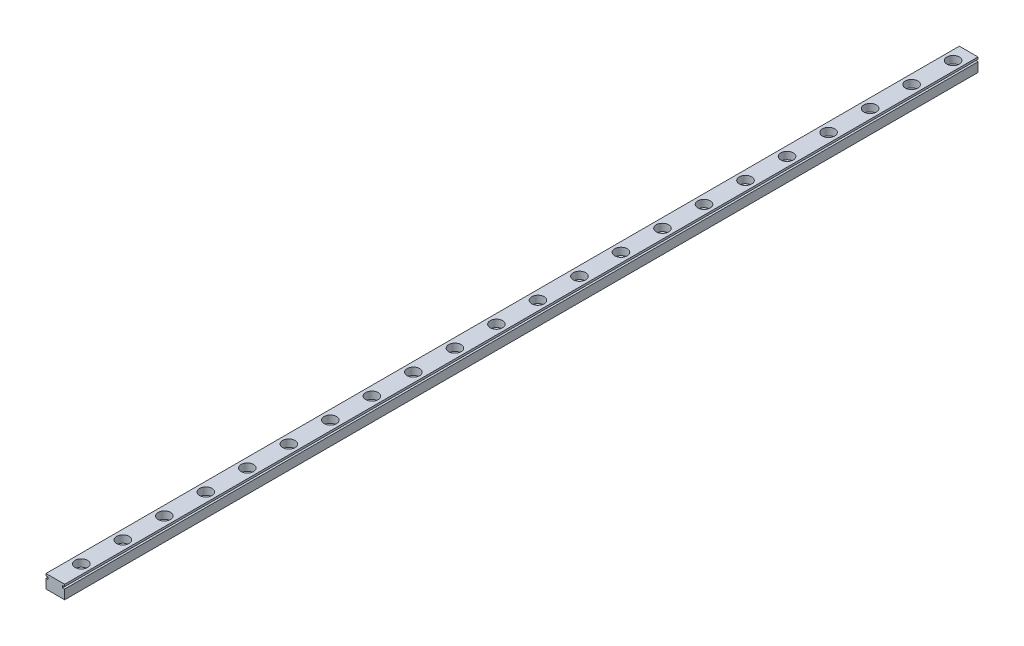
SolidWorks part; units mm, degrees
material "1.0401 (C15)"
ref_plane "前视基准面" through (0, 0, 0) normal (0, 0, 1) x (1, 0, 0)
ref_plane "上视基准面" through (0, 0, 0) normal (0, 1, 0) x (1, 0, 0)
ref_plane "右视基准面" through (0, 0, 0) normal (1, 0, 0) x (0, 0, -1)
sketch "草图1" plane through (0, 0, 0) normal (0, 0, 1) x (1, 0, 0)
  line L0 (0, -0.8589) -> (0, 7.8911) construction
  line L1 (-4.5, 0) -> (4.5, 0)
  line L2 (4.5, 0) -> (4.5, 4.5)
  line L3 (4.5, 5.5) -> (3.5, 5.5)
  line L4 (3.5, 5.5) -> (3.5, 4.5)
  line L5 (4.5, 5.5) -> (4.5, 6.5)
  line L6 (4.5, 6.5) -> (-4.5, 6.5)
  line L7 (3.5, 4.5) -> (4.5, 4.5)
  line L8 (-4.5, 0) -> (-4.5, 4.5)
  line L9 (-3.5, 4.5) -> (-4.5, 4.5)
  line L10 (-3.5, 5.5) -> (-3.5, 4.5)
  line L11 (-4.5, 5.5) -> (-3.5, 5.5)
  line L12 (-4.5, 5.5) -> (-4.5, 6.5)
  point P12 (0, 0)
  point P17 (0, 6.5)
  dimension "D1" = 4.5
  dimension "D2" = 6.5
  dimension "D3" = 1
  dimension "D4" = 1
  dimension "D5" = 1
  dimension "D6" = 4.5
extrude "凸台-拉伸1" add sketch "草图1" along normal blind 440
sketch "草图2" plane through (0, 0, 0) normal (1, 0, 0) x (0, 0, -1)
  line L0 (-7.5, 7.6159) -> (-7.5, -2.728) construction
  line L1 (-7.5, 0) -> (-6, 0)
  line L2 (-440, 0) -> (0, 0) construction
  line L3 (-6, 0) -> (-6, 3)
  line L4 (-6, 3) -> (-4.5, 3)
  line L5 (-4.5, 3) -> (-4.5, 6.5)
  line L6 (-440, 6.5) -> (0, 6.5) construction
  line L7 (-4.5, 6.5) -> (-7.5, 6.5)
  line L8 (-7.5, 0) -> (-7.5, 6.5)
  dimension "D1" = 7.5
  dimension "D2" = 1.5
  dimension "D3" = 3
  dimension "D4" = 3.5
revolve "切除-旋转1" cut sketch "草图2" angle 360 about L0
pattern_linear "阵列(线性)1" count 22 spacing 20 along (0, 0, 1) of "切除-旋转1"
